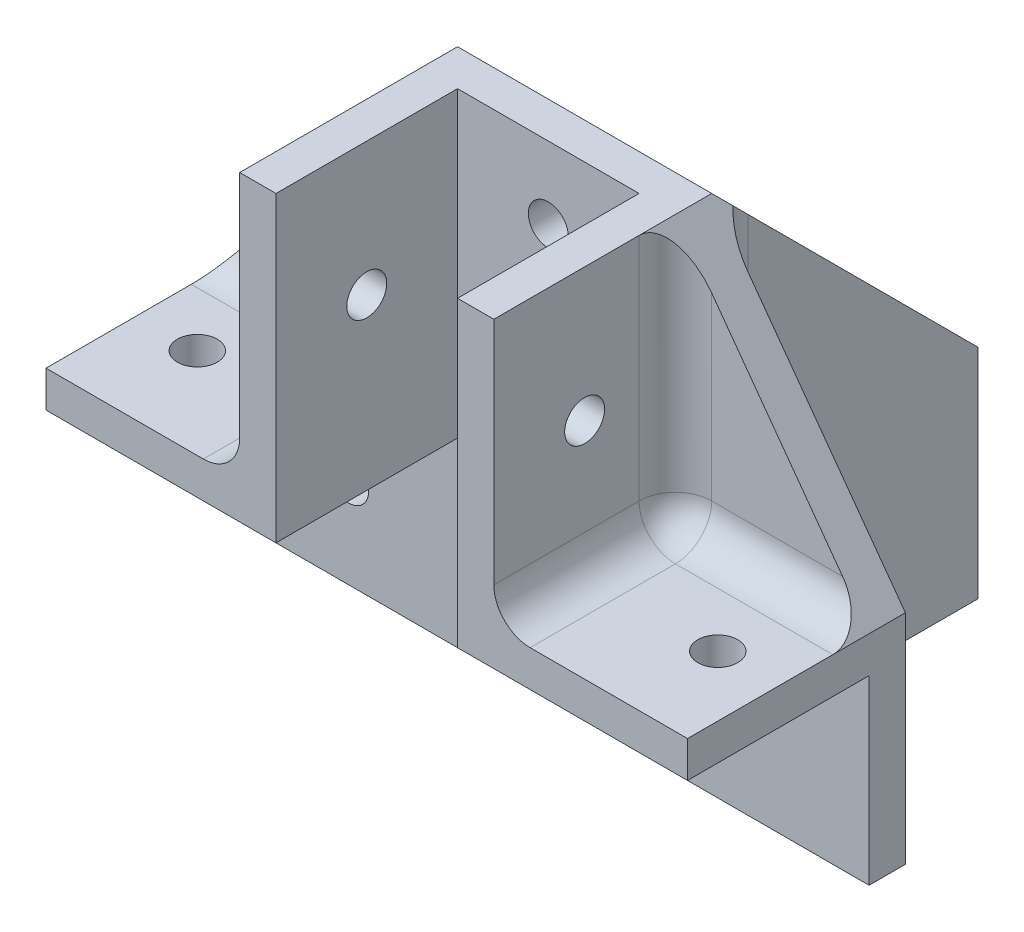
SolidWorks part; units mm, degrees
material "ABS"
ref_plane "前视基准面" through (0, 0, 0) normal (0, 0, 1) x (1, 0, 0)
ref_plane "上视基准面" through (0, 0, 0) normal (0, 1, 0) x (1, 0, 0)
ref_plane "右视基准面" through (0, 0, 0) normal (1, 0, 0) x (0, 0, -1)
other "Configuration Table"
sketch "草图1" plane through (0, 0, 0) normal (0, 1, 0) x (1, 0, 0)
  line L0 (0, 73.0319) -> (0, -39.734) construction
  line L1 (-26.5, -9) -> (26.5, -9)
  line L2 (-26.5, -9) -> (-26.5, 9)
  line L3 (-26.5, 9) -> (26.5, 9) construction
  line L4 (26.5, -9) -> (26.5, 9)
  line L5 (-26.5, -9) -> (26.5, 9) construction
  line L6 (-26.5, 9) -> (26.5, -9) construction
  line L7 (-10.5, -9) -> (10.5, -9)
  line L8 (-10.5, -9) -> (-10.5, 31) construction
  line L9 (-10.5, 31) -> (10.5, 31)
  line L10 (10.5, -9) -> (10.5, 31) construction
  line L11 (-26.5, 9) -> (-10.5, 9)
  line L12 (-10.5, 9) -> (-10.5, 31)
  line L13 (10.5, 31) -> (10.5, 9)
  line L14 (10.5, 9) -> (26.5, 9)
  point P0 (0, 0)
  dimension "D1" = 18
  dimension "D2" = 21
  dimension "D3" = 22
  dimension "D4" = 16
extrude "凸台-拉伸1" add sketch "草图1" along normal blind 18 contours L14 L13 L9 L12 L11 L2 L1 L4 region at (0, 0, -6.5254)
sketch "草图2" plane through (0, 18, 0) normal (0, 1, 0) x (1, 0, 0)
  line L0 (-26.5, -9) -> (26.5, -9) construction
  line L1 (-10.5, 9) -> (10.5, 9)
  line L2 (-10.5, 9) -> (-10.5, -9)
  line L3 (-10.5, -9) -> (10.5, -9)
  line L4 (10.5, 9) -> (10.5, -9)
  line L5 (10.5, 31) -> (10.5, 9) construction
extrude "凸台-拉伸2" add sketch "草图2" along normal blind 22
sketch "草图3" plane through (-26.5, 0, 0) normal (-1, 0, 0) x (0, 0, 1)
  line L1 (9, 0) -> (-6, 0)
  line L2 (9, 0) -> (9, 15)
  line L3 (9, 15) -> (-6, 15)
  line L4 (-6, 0) -> (-6, 15)
  dimension "D1" = 15
extrude "切除-拉伸1" cut sketch "草图3" against normal through all
sketch "草图4" plane through (0, 40, 0) normal (0, 1, 0) x (1, 0, 0)
  line L0 (-10.5, -9) -> (10.5, -9) construction
  line L1 (-7.5, -9) -> (7.5, -9)
  line L2 (-7.5, -9) -> (-7.5, 6)
  line L3 (-7.5, 6) -> (7.5, 6)
  line L4 (7.5, -9) -> (7.5, 6)
  line L5 (10.5, -9) -> (10.5, 9) construction
  line L6 (-10.5, 9) -> (-10.5, -9) construction
  dimension "D1" = 3
  dimension "D2" = 3
extrude "切除-拉伸2" cut sketch "草图4" against normal through all
sketch "草图5" plane through (0, 0, -31) normal (0, 0, -1) x (-1, 0, 0)
  line L0 (10.5, 0) -> (-10.5, 0) construction
  line L1 (-7.5, 0) -> (7.5, 0)
  line L2 (-7.5, 0) -> (-7.5, 15)
  line L3 (-7.5, 15) -> (7.5, 15)
  line L4 (7.5, 0) -> (7.5, 15)
  line L5 (-10.5, 18) -> (-10.5, 0) construction
  line L6 (10.5, 18) -> (10.5, 0) construction
  dimension "D1" = 3
  dimension "D2" = 3
extrude "切除-拉伸3" cut sketch "草图5" against normal through all
sketch "草图6" plane through (0, 0, -9) normal (0, 0, -1) x (-1, 0, 0)
  line L0 (-39.5043, 7.5) -> (41.7715, 7.5) construction
  line L1 (0, 53.696) -> (0, -10.2798) construction
  line L2 (-10.5, 0) -> (-26.5, 0) construction
  line L3 (-10.5, 18) -> (-10.5, 0) construction
  line L4 (10.5, 18) -> (-10.5, 18) construction
  circle A0 centre (-16.5, 7.5) radius 1.65
  circle A1 centre (0, 24) radius 1.65
  circle A3 centre (16.5, 7.5) radius 1.65
  circle A4 centre (0, 34) radius 1.65
  dimension "D2" = 3.3
  dimension "D3" = 6
  dimension "D4" = 6
  dimension "D5" = 10
  dimension "D1" = 7.5
extrude "切除-拉伸4" cut sketch "草图6" against normal through all
sketch "草图7" plane through (0, 18, 0) normal (0, 1, 0) x (1, 0, 0)
  line L0 (-32.5335, -1.5) -> (33.971, -1.5) construction
  line L1 (0, 40.7221) -> (0, -10.8933) construction
  line L2 (-26.5, -9) -> (-10.5, -9) construction
  line L3 (10.5, 9) -> (-10.5, 9) construction
  line L4 (-10.5, 9) -> (-10.5, -9) construction
  circle A0 centre (-21.5, -1.5) radius 1.65
  circle A1 centre (0, 15) radius 1.65
  circle A2 centre (0, 25) radius 1.65
  circle A3 centre (21.5, -1.5) radius 1.65
  dimension "D2" = 3.3
  dimension "D3" = 6
  dimension "D4" = 10
  dimension "D5" = 11
  dimension "D1" = 7.5
extrude "切除-拉伸5" cut sketch "草图7" against normal through all
sketch "草图8" plane through (10.5, 0, 0) normal (1, 0, 0) x (0, 0, -1)
  line L0 (-1.5, 45.4845) -> (-1.5, -8.2993) construction
  line L1 (-18.2111, 7.5) -> (58.2111, 7.5) construction
  line L2 (-9, 40) -> (-9, 18) construction
  line L3 (31, 0) -> (9, 0) construction
  line L5 (-9, 18) -> (9, 18) construction
  line L6 (9, 18) -> (9, 0) construction
  circle A0 centre (-1.5, 29) radius 1.65
  circle A3 centre (20, 7.5) radius 1.65
  dimension "D3" = 3.3
  dimension "D6" = 11
  dimension "D1" = 7.5
  dimension "D2" = 7.5
  dimension "D4" = 11
extrude "切除-拉伸6" cut sketch "草图8" against normal through all
sketch "草图9" plane through (0, 0, -9) normal (0, 0, -1) x (-1, 0, 0)
  line L0 (-10.5, 40) -> (-26.5, 18)
  line L1 (-26.5, 18) -> (-10.5, 18)
  line L2 (-10.5, 18) -> (-10.5, 40)
  line L3 (10.5, 40) -> (26.5, 18)
  line L4 (26.5, 18) -> (10.5, 18)
  line L5 (10.5, 18) -> (10.5, 40)
extrude "凸台-拉伸4" add sketch "草图9" against normal blind 3
sketch "草图10" plane through (10.5, 0, 0) normal (1, 0, 0) x (0, 0, -1)
  line L0 (9, 40) -> (31, 18)
  line L1 (31, 18) -> (9, 18)
  line L2 (9, 18) -> (9, 40)
extrude "凸台-拉伸5" add sketch "草图10" against normal blind 3
sketch "草图11" plane through (-10.5, 0, 0) normal (-1, 0, 0) x (0, 0, 1)
  line L0 (-9, 40) -> (-31, 18)
  line L1 (-31, 18) -> (-9, 18)
  line L2 (-9, 18) -> (-9, 40)
extrude "凸台-拉伸6" add sketch "草图11" against normal blind 3
fillet "圆角1" radius 3 13 edges at (18.5, 18, -6) (10.5, 29, -6) (10.5, 18, 1.5) (10.5, 20, -9) (7.5, 18, -20) (-7.5, 18, -20) (7.5, 29, -9) (-7.5, 29, -9) (0, 18, -9) (-10.5, 20, -9) (-10.5, 18, 1.5) (-18.5, 18, -6) (-10.5, 29, -6)
